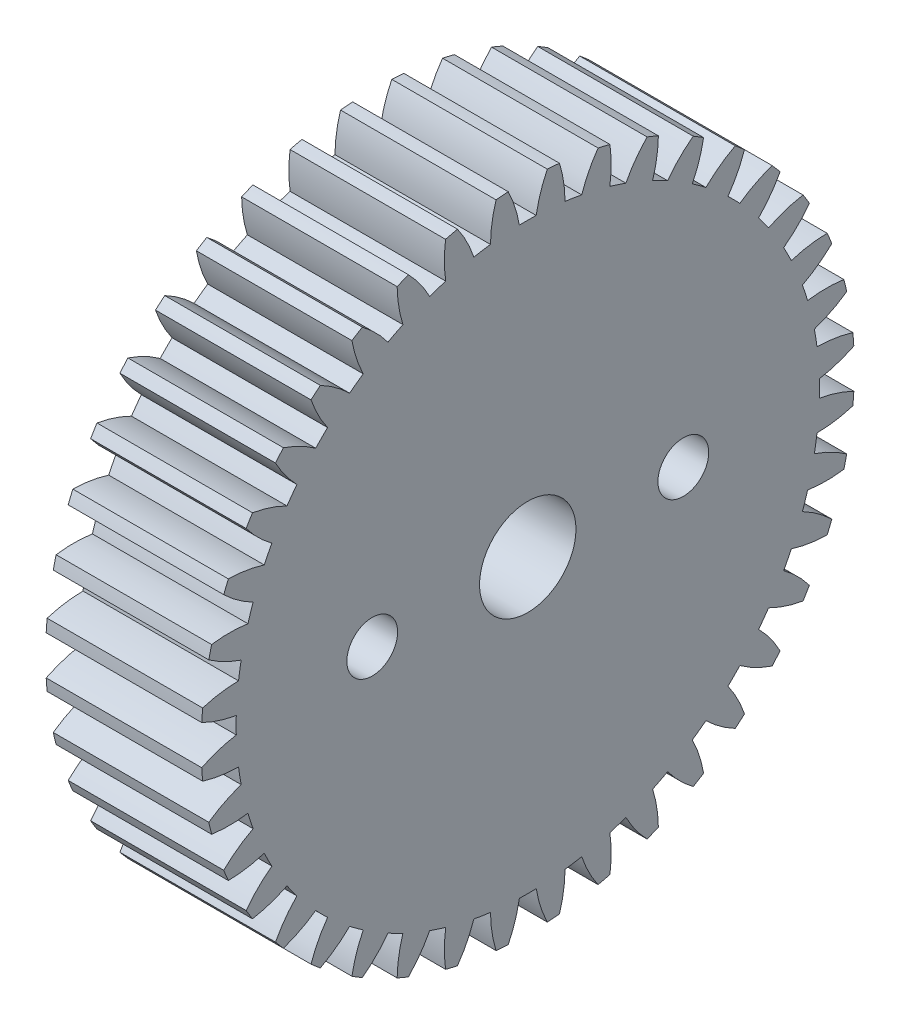
SolidWorks part; units mm, degrees
ref_plane "Plane1" through (0, 0, 0) normal (0, 0, 1) x (1, 0, 0)
ref_plane "Plane2" through (0, 0, 0) normal (0, 1, 0) x (1, 0, 0)
ref_plane "Plane3" through (0, 0, 0) normal (1, 0, 0) x (0, 0, -1)
sketch "HoldingSke" plane through (0, 0, 0) normal (0, 1, 0) x (1, 0, 0)
  line L0 (0, 0) -> (0.766, -0.6428)
  line L1 (-15, 0) -> (100, 0) construction
  line L2 (0, 0) -> (-2.1039, 2.3779)
  line L3 (0, 0) -> (-11.863, 4.5341)
  line L4 (0, 0) -> (6.6156, 5.5511)
  line L5 (0, 0) -> (-46.8476, -17.4728)
  line L6 (0, 0) -> (-8.2896, -5.593)
  line L7 (-2.1039, 2.3779) -> (8.6586, 51.2059)
  line L8 (-76.2, 54.61) -> (-75.2, 54.61)
  line L9 (-67.7845, 28.3722) -> (-49.3413, 33.142)
  line L10 (-76.2, 71.12) -> (104.1128, 71.12)
  line L11 (0, 0) -> (-10, 0)
  line L12 (-76.2, 101.6) -> (-76.162, 101.6)
  line L13 (24.9733, 27.94) -> (52.9518, 28.4284)
  line L14 (24.9733, 27.94) -> (24.9743, 27.94)
  line L15 (24.9733, 27.94) -> (100.4006, 29.5858)
  line L16 (-63.627, -1) -> (-12.827, -1)
  circle A0 centre (0, 0) radius 3
  circle A1 centre (0, 0) radius 18.749
  circle A2 centre (0, 0) radius 37.5
  circle A3 centre (0, 0) radius 3
  dimension "MHD" = 37.498
  dimension "Hub_dia" = 75
  dimension "Bore" = 6
  dimension "MBD" = 6
  dimension "Num_teeth" = 40
  dimension "Pitch" = 1
  dimension "Overall_len" = 50
  dimension "Show_teeth" = 40
  dimension "Thickness" = 10
  dimension "OAL" = 50.0001
  dimension "T_dim" = 1
  dimension "Ap" = 14.5
  dimension "H" = 19.05
  dimension "Pitch_radius" = 180.3128
  dimension "Width" = 10
  dimension "Backlash" = 0.038
  dimension "Addendum_fac" = 1
  dimension "Dedendum_fac" = 1.25
  dimension "Clearance_fac" = 0.25
  dimension "Dedendum_add" = 0.001
  dimension "Module" = 1
sketch "BasProSke" plane through (0, 0, 0) normal (0, 1, 0) x (1, 0, 0)
  line L0 (-10, 0) -> (60, 0) construction
  line L1 (0, 0) -> (0, 21)
  line L2 (0, 0) -> (10, 0)
  line L3 (10, 0) -> (10, 21)
  line L4 (10, 21) -> (0, 21)
  dimension "Thickness" = 10
  dimension "Diameter" = 42
revolve "Base-Revolve" add sketch "BasProSke" angle 360 about L0
sketch "TooCutSke" plane through (0, 0, 0) normal (1, 0, 0) x (0, 0, -1)
  line L1 (0, 0) -> (0, 107) construction
  line L2 (0, 0) -> (-0.8517, 19.9819) construction
  line L3 (0, 0) -> (-3.1363, 39.8509) construction
  line L4 (-0.8517, 19.9819) -> (-1.5682, 19.9255) construction
  arc A0 (0.5419, 18.7412) -> (-0.5419, 18.7412) centre (0, 0) ccw
  arc A1 (1.2681, 20.9871) -> (-1.2681, 20.9871) centre (0, 0) ccw
  circle A2 centre (0, 0) radius 20 construction
  circle A3 centre (0, 0) radius 19.363 construction
  arc A4 (-0.5419, 18.7412) -> (-1.2681, 20.9871) centre (-8.4337, 17.4298) ccw
  arc A5 (1.2681, 20.9871) -> (0.5419, 18.7412) centre (8.4337, 17.4298) ccw
  dimension "Root_dia" = 37.498
  dimension "Overcut_dia" = 42.0508
  dimension "Pitch_dia" = 40
  dimension "Base_dia" = 38.7259
  dimension "Flank_rad" = 8
  dimension "Half_ang" = 4.5
  dimension "Half_CT" = 0.7187
extrude "ToothCut" cut sketch "TooCutSke" along normal through all
fillet "Breaks" [suppressed] radius 0.02 tangent propagation no
fillet "RootFillets" [suppressed] radius 0.251
pattern_circular "TeethCuts" count 40 every 9 about axis through (-10, 0, 0) along (1, 0, 0) of "ToothCut", "RootFillets", "Breaks"
sketch "HubNeaOneSke" plane through (0, 0, 0) normal (-1, 0, 0) x (0, 0, 1)
  circle A0 centre (0, 0) radius 18.749
  dimension "Diameter" = 37.498
extrude "HubNearOne" [suppressed] add sketch "HubNeaOneSke" along normal blind 40.0001
sketch "HubNeaBotSke" plane through (0, 0, 0) normal (-1, 0, 0) x (0, 0, 1)
  circle A0 centre (0, 0) radius 18.749
  dimension "Diameter" = 37.498
extrude "HubNearBoth" [suppressed] add sketch "HubNeaBotSke" along normal blind 20
ref_plane "FarPln" through (10, 0, 0) normal (1, 0, 0) x (0, 0, -1)
sketch "HubFarSke" plane through (10, 0, 0) normal (1, 0, 0) x (0, 0, -1)
  circle A0 centre (0, 0) radius 18.749
  dimension "Diameter" = 37.498
extrude "HubFar" [suppressed] add sketch "HubFarSke" along normal blind 20
sketch "BorSke" plane through (0, 0, 0) normal (1, 0, 0) x (0, 0, -1)
  circle A0 centre (0, 0) radius 3
  dimension "Diameter" = 6
extrude "Bore" cut sketch "BorSke" along normal mid plane 100.0001
sketch "KeySke" plane through (0, 0, 0) normal (1, 0, 0) x (0, 0, -1)
  line L0 (-1, 0) -> (-1, 4)
  line L1 (-1, 4) -> (1, 4)
  line L2 (1, 4) -> (1, 0)
  line L3 (0, 0) -> (0, 34) construction
  line L4 (-1, 0) -> (1, 0)
  dimension "Offset" = 4
  dimension "Width" = 2
extrude "Keyway" [suppressed] cut sketch "KeySke" along normal mid plane 100.0001
pattern_circular "Keyway2" [suppressed] count 2 every 90 about axis through (-10, 0, 0) along (1, 0, 0) reverse direction yes
hole_wizard "#4 Clearance Hole1" positions "Sketch1" profile "Sketch2" hole size "#4" standard "ANSI Inch" end condition through all
sketch "Sketch1" plane through (10, 0, 0) normal (1, 0, 0) x (0, 0, -1)
  circle A0 centre (0, 0) radius 3 construction
  point P0 (-10, 0)
  point P2 (10, 0)
  dimension "D1" = 10
  dimension "D2" = 10
  dimension "D3" = 0
sketch "Sketch2" plane through (10, 0, 10) normal (0, 1, 0) x (0, 0, -1)
  line L0 (0, 0) -> (0, 10)
  line L1 (0, 10) -> (1.6319, 10)
  line L2 (1.6319, 10) -> (1.632, 0)
  line L5 (1.632, 0) -> (0, 0)
  line L11 (0, -6.35) -> (0, 107.95) construction
  dimension "Thru Hole Dia." = 3.2639
  dimension "Thru Hole Depth" = 10
sketch "Sketch3" plane through (10, 0, 0) normal (1, 0, 0) x (0, 0, -1)
  circle A0 centre (0, 0) radius 3.1
  dimension "D1" = 6.2
extrude "Cut-Extrude1" cut sketch "Sketch3" against normal through all
equation "' \"Module@HoldingSke\" = 6.35"
equation "' \"Num_teeth@HoldingSke\" = 12"
equation "' \"Ap@HoldingSke\" =  20"
equation "' \"Ap@HoldingSke\" = 20"
equation "' \"Width@HoldingSke\" = 0.5 * 25.4"
equation "' \"Hub_dia@HoldingSke\"= 1 * 25.4"
equation "' \"Hub_dia@HoldingSke\" = 1 * 25.4"
equation "' \"Overall_len@HoldingSke\" = 1.0 * 25.4"
equation "' \"Bore@HoldingSke\" = 0.75 * 25.4"
equation "' \"T_dim@HoldingSke\" = 0.1 * 25.4"
equation "' \"Width@KeySke\" = 0.25 * 25.4"
equation "' \"Show_teeth@HoldingSke\" = 13"
equation "' \"Backlash@HoldingSke\" = 0.009 * 25.4"
equation "' \"Addendum_fac@HoldingSke\" = 1.0"
equation "' \"Dedendum_fac@HoldingSke\" = 1.25"
equation "' \"Dedendum_add@HoldingSke\" = 0.00005 * 25.4"
equation "' \"Clearance_fac@HoldingSke\" = 0.25"
equation "\"Pitch@HoldingSke\" = 1 / \"Module@HoldingSke\""
equation "\"Overcut_dia@TooCutSke\" = (\"Num_teeth@HoldingSke\" + 2 * \"Addendum_fac@HoldingSke\") / \"Pitch@HoldingSke\" + 0.002 * 25.4"
equation "\"Pitch_dia@TooCutSke\" = \"Num_teeth@HoldingSke\" / \"Pitch@HoldingSke\""
equation "\"Base_dia@TooCutSke\" = \"Num_teeth@HoldingSke\" / \"Pitch@HoldingSke\" * cos((\"Ap@HoldingSke\"  * 3.14159265 / 180))"
equation "\"Root_dia@TooCutSke\" = (\"Num_teeth@HoldingSke\" + 2) / \"Pitch@HoldingSke\" - 2 * (\"Addendum_fac@HoldingSke\" + \"Dedendum_fac@HoldingSke\") / \"Pitch@HoldingSke\" - \"Dedendum_add@HoldingSke\" * 2"
equation "\"Half_ang@TooCutSke\" = 180 / \"Num_teeth@HoldingSke\""
equation "\"Half_CT@TooCutSke\" = \"Num_teeth@HoldingSke\" / \"Pitch@HoldingSke\" * sin((3.14159265 / 2 / \"Num_teeth@HoldingSke\")) / 2 - 7 * \"Backlash@HoldingSke\" / 4"
equation "\"Flank_rad@TooCutSke\" = \"Num_teeth@HoldingSke\" / \"Pitch@HoldingSke\" / 5"
equation "\"Radius@RootFillets\" = \"Clearance_fac@HoldingSke\" / \"Pitch@HoldingSke\" + \"Dedendum_add@HoldingSke\""
equation "\"Break_rad@Breaks\" = 0.02 / \"Pitch@HoldingSke\""
equation "\"Thickness@HoldingSke\" = \"Width@HoldingSke\""
equation "\"OAL@HoldingSke\" = \"Thickness@HoldingSke\""
equation "\"MHD@HoldingSke\" = (\"Num_teeth@HoldingSke\" + 2) / \"Pitch@HoldingSke\" - 2 * (\"Addendum_fac@HoldingSke\" + \"Dedendum_fac@HoldingSke\")  / \"Pitch@HoldingSke\" - \"Dedendum_add@HoldingSke\" * 2"
equation "\"MBD@HoldingSke\" = (\"Num_teeth@HoldingSke\" + 2) / \"Pitch@HoldingSke\" - 2 * (\"Addendum_fac@HoldingSke\" + \"Dedendum_fac@HoldingSke\")  / \"Pitch@HoldingSke\" - \"Dedendum_add@HoldingSke\" * 2 - 0.002 * 25.4"
equation "\"MHD@HoldingSke\" = ((sgn( \"MHD@HoldingSke\" - \"Hub_dia@HoldingSke\" )-1)*( \"MHD@HoldingSke\" - \"Hub_dia@HoldingSke\" ))/-2+ \"Hub_dia@HoldingSke\""
equation "\"MBD@HoldingSke\" = ((sgn( \"MBD@HoldingSke\" - \"Bore@HoldingSke\" )-1)*( \"MBD@HoldingSke\" - \"Bore@HoldingSke\" ))/-2+ \"Bore@HoldingSke\""
equation "\"OAL@HoldingSke\" = ((sgn( \"OAL@HoldingSke\" - \"Overall_len@HoldingSke\" )+1)*( \"OAL@HoldingSke\" - \"Overall_len@HoldingSke\" ))/2 + \"Overall_len@HoldingSke\" + 0.000002 * 25.4"
equation "\"Num_teeth@TeethCuts\" = int( \"Show_teeth@HoldingSke\" ) + 1"
equation "\"Num_teeth@TeethCuts\" = ((sgn( \"Num_teeth@TeethCuts\" - \"Num_teeth@HoldingSke\" )-1)*( \"Num_teeth@TeethCuts\" - \"Num_teeth@HoldingSke\" ))/-2+ \"Num_teeth@HoldingSke\""
equation "\"Num_teeth@TeethCuts\" = ((sgn( \"Num_teeth@TeethCuts\" - 2.0)+1)*( \"Num_teeth@TeethCuts\" - 2.0))/2 +2.0"
equation "\"Angle@TeethCuts\" = 360.0 / \"Num_teeth@HoldingSke\""
equation "\"Diameter@BasProSke\" = (\"Num_teeth@HoldingSke\" + 2 * \"Addendum_fac@HoldingSke\") / \"Pitch@HoldingSke\""
equation "\"Thickness@BasProSke\"  = \"Thickness@HoldingSke\""
equation "' \"Fillet_rad@BasProSke\" =  \"Thickness@HoldingSke\" * 0.05"
equation "' \"Fillet_rad@BasProSke\" = \"Thickness@HoldingSke\" * 0.05"
equation "\"MHD@HoldingSke\" = ((sgn( \"MHD@HoldingSke\" - \"Root_dia@TooCutSke\" )-1)*( \"MHD@HoldingSke\" - \"Root_dia@TooCutSke\" ))/-2+ \"Root_dia@TooCutSke\""
equation "\"Diameter@HubNeaOneSke\" = \"MHD@HoldingSke\""
equation "\"Length@HubNearOne\" = \"OAL@HoldingSke\" - \"Thickness@BasProSke\""
equation "\"Diameter@HubNeaBotSke\" = \"MHD@HoldingSke\""
equation "\"Length@HubNearBoth\" = ( \"OAL@HoldingSke\" - \"Thickness@BasProSke\" ) / 2.0"
equation "\"Thickness@FarPln\" = \"Thickness@BasProSke\""
equation "\"Diameter@HubFarSke\" = \"MHD@HoldingSke\""
equation "\"Length@HubFar\" = ( \"OAL@HoldingSke\" - \"Thickness@BasProSke\" ) / 2.0"
equation "\"Diameter@BorSke\" = \"MBD@HoldingSke\""
equation "\"D1@Bore\" = \"OAL@HoldingSke\" * 2.0"
equation "\"D1@Keyway\" = \"OAL@HoldingSke\" * 2.0"
equation "\"Offset@KeySke\" = \"T_dim@HoldingSke\" + \"MBD@HoldingSke\" / 2.0"
